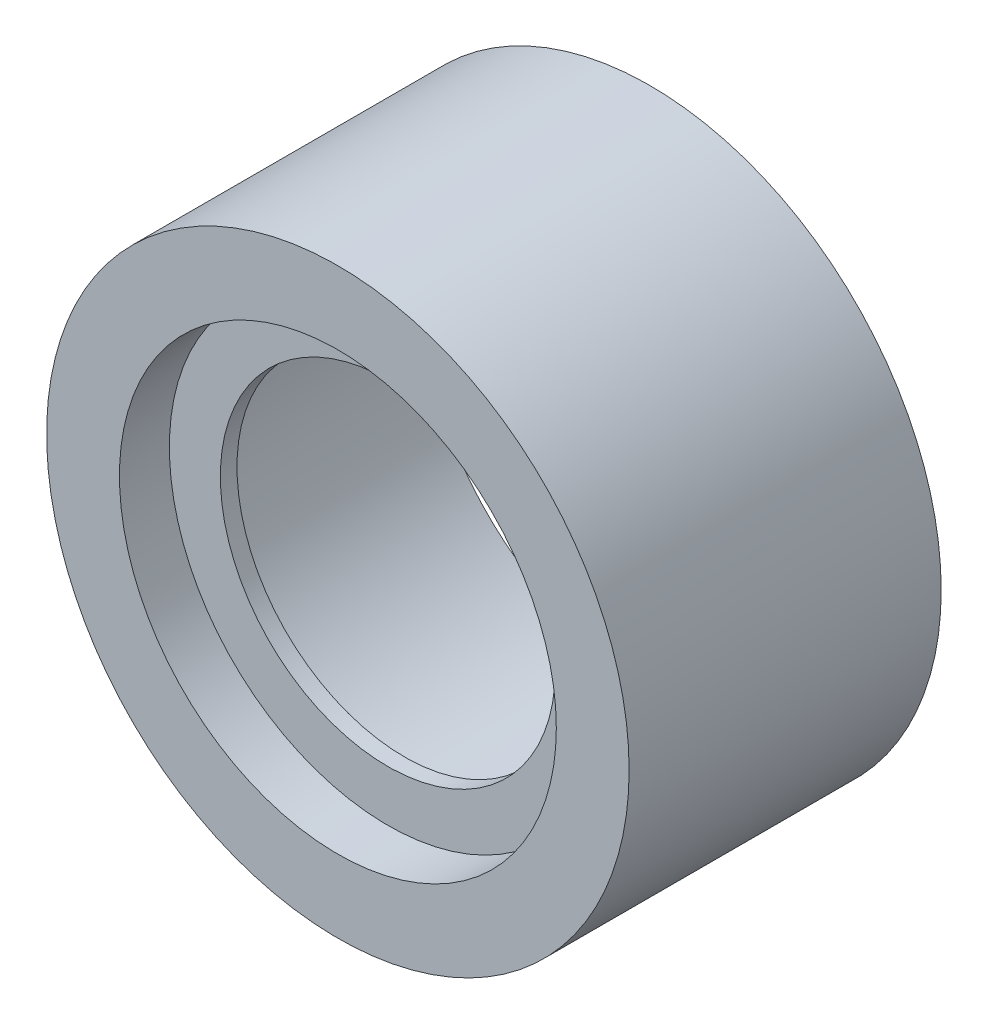
SolidWorks part; units mm, degrees
ref_plane "Front Plane" through (0, 0, 0) normal (0, 0, 1) x (1, 0, 0)
ref_plane "Top Plane" through (0, 0, 0) normal (0, 1, 0) x (1, 0, 0)
ref_plane "Right Plane" through (0, 0, 0) normal (1, 0, 0) x (0, 0, -1)
sketch "Sketch1" plane through (0, 0, 0) normal (1, 0, 0) x (0, 0, -1)
  line L0 (-84.7958, 52.5) -> (-72.7958, 52.5)
  line L1 (-73.3513, 52.5) -> (-74.0979, 52.5) construction
  line L3 (-50.0958, 55) -> (-67.2958, 55) construction
  line L4 (-84.7958, 52.5) -> (-84.7958, 70)
  line L5 (-84.7958, 70) -> (-9.7958, 70)
  line L6 (-72.7958, -51.9444) -> (-72.7958, 51.9445) construction
  line L7 (-72.7958, 52.5) -> (-72.7958, 40.25)
  line L8 (-72.7958, -48.3333) -> (-72.7958, 48.3333) construction
  line L9 (-72.7958, 40.25) -> (-68.7958, 40.25)
  line L10 (-68.7958, 53.5) -> (-68.7958, -53.5) construction
  line L11 (-68.7958, 40.25) -> (-68.7958, 55)
  line L12 (-68.7958, 55) -> (-9.7958, 55)
  line L14 (-9.7958, 70) -> (-9.7958, 55)
  line L15 (-68.7958, 40) -> (-82.7958, 40) construction
  line L16 (174.1864, 0) -> (-154.8488, 0) construction
  line L17 (-82.7958, 51.3889) -> (-82.7958, -51.3889) construction
  line L18 (-163.8227, 0) -> (139.4858, 0) construction
  dimension "D1" = 0.25
  dimension "D2" = 70
  dimension "D3" = 75
  dimension "D4" = 2
revolve "Revolve1" add sketch "Sketch1" angle 360 about L18
sketch "Sketch2" plane through (0, 0, 9.7958) normal (0, 0, -1) x (-1, 0, 0)
  line L0 (0, 62.5) -> (0, -62.5) construction
  circle A0 centre (0, 0) radius 62.5 construction
  circle A1 centre (0, 62.5) radius 4
  circle A2 centre (0, -62.5) radius 4
  dimension "D1" = 125
  dimension "D2" = 8
extrude "Cut-Extrude1" cut sketch "Sketch2" against normal blind 10
sketch "Sketch5" plane through (0, 0, 0) normal (0, 0, 1) x (1, 0, 0)
  line L0 (0, 70) -> (0, -70) construction
  line L3 (-31.25, 54.1266) -> (0, 0) construction
  line L8 (0, 62.5) -> (0, 0) construction
  line L9 (31.25, 54.1266) -> (0, 0) construction
  line L10 (54.1266, 31.25) -> (0, 0) construction
  line L11 (62.5, 0) -> (0, 0) construction
  line L12 (54.1266, -31.25) -> (0, 0) construction
  line L13 (31.25, -54.1266) -> (0, 0) construction
  line L14 (0, -62.5) -> (0, 0) construction
  line L15 (-31.25, -54.1266) -> (0, 0) construction
  line L16 (-54.1266, -31.25) -> (0, 0) construction
  line L17 (-62.5, 0) -> (0, 0) construction
  line L18 (-54.1266, 31.25) -> (0, 0) construction
  circle A0 centre (0, 0) radius 62.5 construction
  point P12 (-31.25, 54.1266)
  point P14 (-62.5, 0)
  point P15 (31.25, 54.1266)
  point P17 (62.5, 0)
  point P27 (54.1266, -31.25)
  point P28 (31.25, -54.1266)
  point P30 (-31.25, -54.1266)
  point P31 (-54.1266, -31.25)
  point P33 (-54.1266, 31.25)
  point P34 (-9.7842, -27.7218)
  dimension "D1" = 125
  dimension "D3" = 12
  dimension "D2" = 30
hole_wizard "M8x1.25 Tapped Hole2" positions "Sketch5" profile "Sketch6" tap size "M8x1.25" standard "ANSI Metric"
sketch "Sketch6" plane through (-54.1266, 31.25, 0) normal (1, 0, 0) x (0, 1, 0)
  line L0 (0, 0) -> (0, 21.7929)
  line L1 (0, 21.7929) -> (3.4, 19.75)
  line L2 (3.4, 19.75) -> (3.4, 0)
  line L5 (3.4, 0) -> (0, 0)
  line L10 (0, 21.7929) -> (-3.4, 19.75) construction
  line L11 (0, -6.35) -> (0, 107.95) construction
  dimension "Tap Drill Dia." = 6.8
  dimension "Tap Drill Depth" = 19.75
  dimension "Drill Angle" = 118
cosmetic thread "Hole Thread8" parameters "D1"=16, "D2"=8
cosmetic thread "Hole Thread9" parameters "D1"=16, "D2"=8
cosmetic thread "Hole Thread10" parameters "D1"=16, "D2"=8
cosmetic thread "Hole Thread11" parameters "D1"=16, "D2"=8
cosmetic thread "Hole Thread12" parameters "D1"=16, "D2"=8
cosmetic thread "Hole Thread13" parameters "D1"=16, "D2"=8
cosmetic thread "Hole Thread14" parameters "D1"=16, "D2"=8
cosmetic thread "Hole Thread15" parameters "D1"=16, "D2"=8
cosmetic thread "Hole Thread16" parameters "D1"=16, "D2"=8
